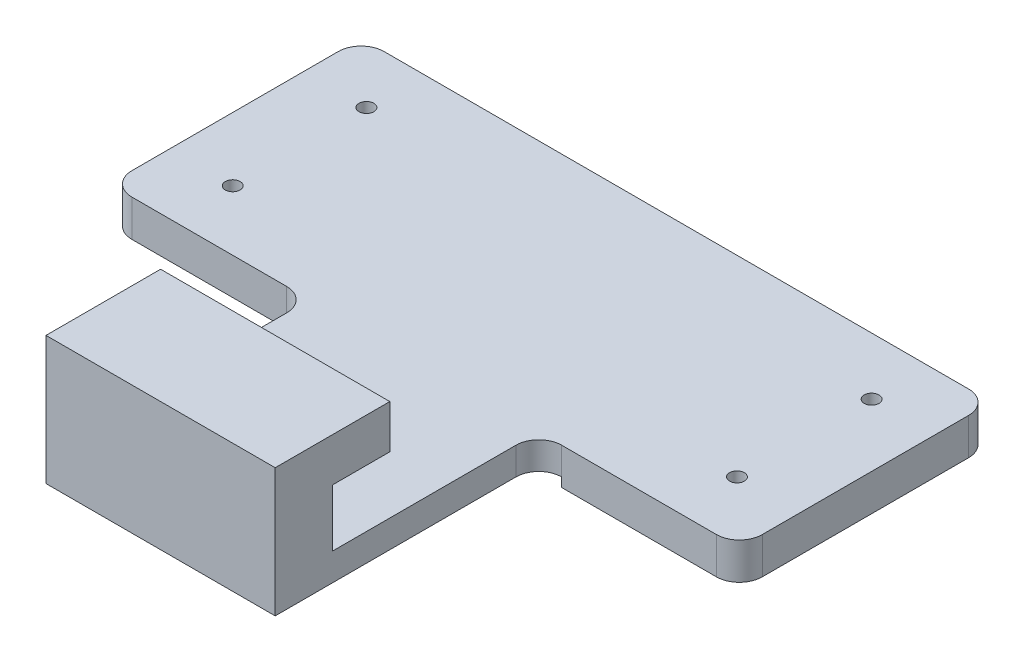
SolidWorks part; units mm, degrees
note: The reader was unsure of these and kept them because the rebuilt part matched: shared geometry of "Sketch5<3>".
ref_plane "Front Plane" through (0, 0, 0) normal (0, 0, 1) x (1, 0, 0)
ref_plane "Top Plane" through (0, 0, 0) normal (0, 1, 0) x (1, 0, 0)
ref_plane "Right Plane" through (0, 0, 0) normal (1, 0, 0) x (0, 0, -1)
sketch "Sketch1" plane through (0, 0, 0) normal (0, 1, 0) x (1, 0, 0)
  line L1 (-34.925, -28.575) -> (34.925, -28.575)
  line L2 (-34.925, -28.575) -> (-34.925, 28.575)
  line L3 (-34.925, 28.575) -> (34.925, 28.575)
  line L4 (34.925, -28.575) -> (34.925, 28.575)
  line L5 (-34.925, -28.575) -> (34.925, 28.575) construction
  line L6 (-34.925, 28.575) -> (34.925, -28.575) construction
  point P0 (0, 0)
  dimension "D1" = 57.15
  dimension "D2" = 69.85
extrude "Boss-Extrude1" add sketch "Sketch1" along normal blind 15.24
sketch "Sketch2" plane through (-34.925, 0, 0) normal (-1, 0, 0) x (0, 0, 1)
  line L0 (-28.575, 15.24) -> (-28.575, 0) construction
  line L1 (-28.575, 10.414) -> (22.225, 10.414)
  line L2 (-28.575, 10.414) -> (-28.575, 4.064)
  line L3 (-28.575, 4.064) -> (22.225, 4.064)
  line L4 (22.225, 10.414) -> (22.225, 4.064)
  dimension "D1" = 6.35
  dimension "D2" = 50.8
  dimension "D3" = 4.064
extrude "Cut-Extrude1" cut sketch "Sketch2" against normal up to surface (69.85 mm away) up to face at (34.925, 7.62, 0)
sketch "Sketch3" plane through (-34.925, 0, 0) normal (-1, 0, 0) x (0, 0, 1)
  line L0 (22.225, 10.414) -> (-28.575, 10.414) construction
  line L1 (-28.575, 15.24) -> (15.875, 15.24)
  line L2 (-28.575, 15.24) -> (-28.575, 10.414)
  line L3 (-28.575, 10.414) -> (15.875, 10.414)
  line L4 (15.875, 15.24) -> (15.875, 10.414)
  dimension "D1" = 44.45
extrude "Cut-Extrude2" cut sketch "Sketch3" against normal blind 50.8
mirror "Mirror1" about plane through (0, 0, 0) normal (1, 0, 0) of "Cut-Extrude2"
sketch "Sketch5" plane through (0, 0, 0) normal (0, -1, 0) x (1, 0, 0)
  line L0 (-27.9908, -22.225) -> (27.9908, -22.225) construction
  line L3 (-30.861, -4.765) -> (30.861, -4.765)
  line L4 (-30.861, -4.765) -> (-30.861, -24.765)
  line L5 (-30.861, -24.765) -> (30.861, -24.765)
  line L6 (30.861, -4.765) -> (30.861, -24.765)
  line L7 (34.925, -28.575) -> (-34.925, -28.575) construction
  line L8 (-27.8892, -7.305) -> (27.9908, -7.305) construction
  circle A0 centre (-27.9908, -22.225) radius 0.8192
  circle A1 centre (27.9908, -22.225) radius 0.8192
  circle A2 centre (-27.8892, -7.305) radius 0.8191
  circle A3 centre (27.9908, -7.305) radius 0.8192
  point P0 (-27.9908, -22.225)
  point P1 (27.9908, -22.225)
  point P2 (0, -22.225)
  point P12 (0, -24.765)
  point P17 (-27.8892, -7.305)
  point P18 (0, -24.765)
  point P20 (27.9908, -7.305)
  dimension "D5" = 1.6383
  dimension "D6" = 1.6383
  dimension "D9" = 1.6383
  dimension "D10" = 1.6383
  dimension "D1" = 2.54
  dimension "D2" = 55.9816
  dimension "D3" = 20
  dimension "D4" = 61.722
  dimension "D7" = 3.81
  dimension "D8" = 2.54
  dimension "D11" = 55.88
extrude "Cut-Extrude3" cut sketch "Sketch5" against normal blind 1.016
extrude "Cut-Extrude4" cut sketch "Sketch5<3>" against normal through all
sketch "Sketch5<3>" plane through (0, 0, 0) normal (0, -1, 0) x (1, 0, 0) same geometry as "Sketch5"
sketch "Sketch7" plane through (0, 0, 22.225) normal (0, 0, -1) x (-1, 0, 0)
  line L0 (-34.925, 15.24) -> (34.925, 15.24) construction
  line L1 (-34.925, 9.144) -> (34.925, 9.144)
  line L2 (-34.925, 9.144) -> (-34.925, 15.24)
  line L3 (-34.925, 15.24) -> (34.925, 15.24)
  line L4 (34.925, 9.144) -> (34.925, 15.24)
  line L5 (-34.925, 9.144) -> (34.925, 15.24) construction
  line L6 (-34.925, 15.24) -> (34.925, 9.144) construction
  line L7 (-34.925, 4.064) -> (34.925, 4.064) construction
  point P0 (0, 12.192)
  dimension "D1" = 5.08
  dimension "D2" = 69.85
extrude "Boss-Extrude2" add sketch "Sketch7" along normal blind 6.35
sketch "Sketch8" plane through (-34.925, 0, 0) normal (-1, 0, 0) x (0, 0, 1)
  line L0 (15.875, 10.414) -> (22.225, 10.414)
  line L1 (15.875, 9.144) -> (15.875, 15.24) construction
  line L3 (15.875, 9.144) -> (22.225, 9.144) construction
  line L5 (22.225, 9.144) -> (22.225, 4.064) construction
  line L6 (15.875, 10.414) -> (15.875, 9.144)
  line L7 (15.875, 9.144) -> (22.225, 9.144)
  line L8 (22.225, 9.144) -> (22.225, 10.414)
  dimension "D1" = 1.27
  dimension "D2" = 1.27
extrude "Cut-Extrude9" cut sketch "Sketch8" against normal through all both and the other way through all
sketch "Sketch17" plane through (0, 0, 15.875) normal (0, 0, -1) x (-1, 0, 0)
  line L0 (-34.925, 15.24) -> (34.925, 15.24) construction
  line L1 (-12.7, 15.24) -> (12.7, 15.24)
  line L2 (-12.7, 15.24) -> (-12.7, 10.414)
  line L3 (-12.7, 10.414) -> (12.7, 10.414)
  line L4 (12.7, 15.24) -> (12.7, 10.414)
  line L7 (-12.7, 15.24) -> (-34.925, 15.24)
  line L8 (-12.7, 15.24) -> (-12.7, 10.414)
  line L9 (-12.7, 10.414) -> (-34.925, 10.414)
  line L10 (-34.925, 15.24) -> (-34.925, 10.414)
  line L11 (12.7, 15.24) -> (34.925, 15.24)
  line L12 (12.7, 15.24) -> (12.7, 10.414)
  line L13 (12.7, 10.414) -> (34.925, 10.414)
  line L14 (34.925, 15.24) -> (34.925, 10.414)
  line L16 (-34.925, 10.414) -> (-34.925, 15.24) construction
  line L17 (34.925, 10.414) -> (34.925, 15.24) construction
  line L18 (-34.925, 10.414) -> (34.925, 10.414) construction
  point P13 (0, 15.24)
  dimension "D1" = 25.4
extrude "Cut-Extrude13" cut sketch "Sketch17" against normal up to surface (6.35 mm away)
sketch "Sketch18" plane through (0, 15.24, 0) normal (0, 1, 0) x (1, 0, 0)
  line L0 (-12.7, -22.225) -> (-12.7, -15.875) construction
  line L1 (-34.925, -28.575) -> (-12.7, -28.575)
  line L2 (-34.925, -28.575) -> (-34.925, 0.635)
  line L3 (-34.925, 0.635) -> (-12.7, 0.635)
  line L4 (-12.7, -28.575) -> (-12.7, 0.635)
  line L5 (12.7, -22.225) -> (12.7, -15.875) construction
  line L6 (34.925, -28.575) -> (12.7, -28.575)
  line L7 (34.925, -28.575) -> (34.925, 0.635)
  line L8 (34.925, 0.635) -> (12.7, 0.635)
  line L9 (12.7, -28.575) -> (12.7, 0.635)
  dimension "D1" = 29.21
extrude "Cut-Extrude14" cut sketch "Sketch18" against normal through all both and the other way through all
fillet "Fillet1" radius 2.54 6 edges at (-34.925, 2.032, -0.635) (-34.925, 2.032, -28.575) (34.925, 2.032, -28.575) (34.925, 2.032, -0.635) (12.7, 2.032, -0.635) (-12.7, 2.032, -0.635)
sketch "Sketch19" plane through (0, 0, 0) normal (0, -1, 0) x (1, 0, 0)
  line L0 (-12.7, 28.575) -> (12.7, 28.575) construction
  line L1 (-15.24, 28.575) -> (15.24, 28.575)
  line L2 (-15.24, 28.575) -> (-15.24, -4.765)
  line L3 (-15.24, -4.765) -> (15.24, -4.765)
  line L4 (15.24, 28.575) -> (15.24, -4.765)
  line L5 (-30.861, -4.765) -> (30.861, -4.765) construction
  point P6 (0, -4.765)
  dimension "D1" = 15.24
extrude "Cut-Extrude16" cut sketch "Sketch19" against normal up to surface (1.016 mm away) up to face at (27.9908, 1.016, -23.0441)
